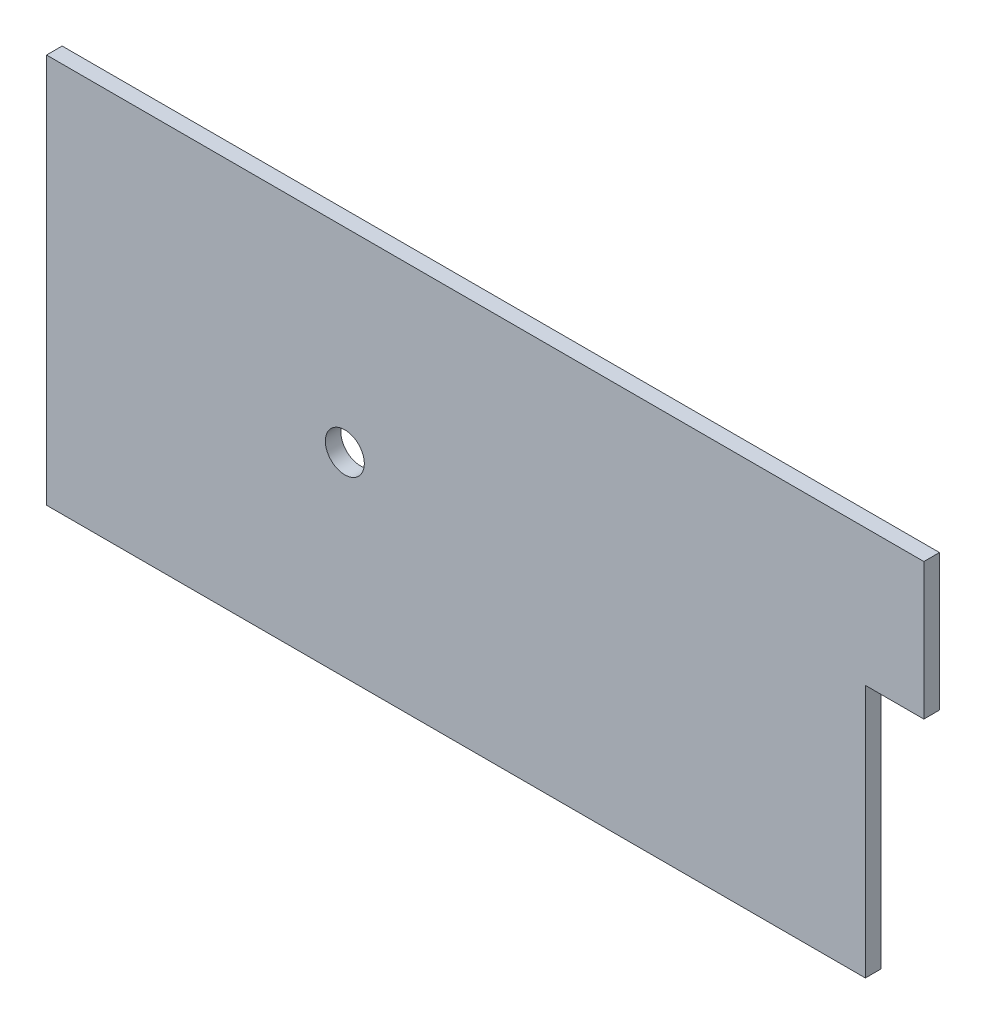
SolidWorks part; units mm, degrees
ref_plane "Front Plane" through (0, 0, 0) normal (0, 0, 1) x (1, 0, 0)
ref_plane "Top Plane" through (0, 0, 0) normal (0, 1, 0) x (1, 0, 0)
ref_plane "Right Plane" through (0, 0, 0) normal (1, 0, 0) x (0, 0, -1)
sketch "Sketch1" plane through (0, 0, 0) normal (0, 0, 1) x (1, 0, 0)
  line L0 (60, 50) -> (75, 50)
  line L1 (-150, -50) -> (60, -50)
  line L2 (-150, -50) -> (-150, 50)
  line L3 (-150, 50) -> (60, 50)
  line L4 (60, -50) -> (60, 50) construction
  line L5 (75, 50) -> (75, 15)
  line L6 (75, 15) -> (60, 15)
  line L13 (60, 15) -> (60, -50)
  circle A2 centre (-73.5, 0) radius 5
  point P1 (0, 0)
  point P9 (0, 0)
  dimension "D3" = 35
  dimension "D4" = 15
  dimension "D1" = 150
  dimension "D2" = 100
  dimension "D8" = 73.5
  dimension "D9" = 60
extrude "Boss-Extrude1" add sketch "Sketch1" along normal blind 4
